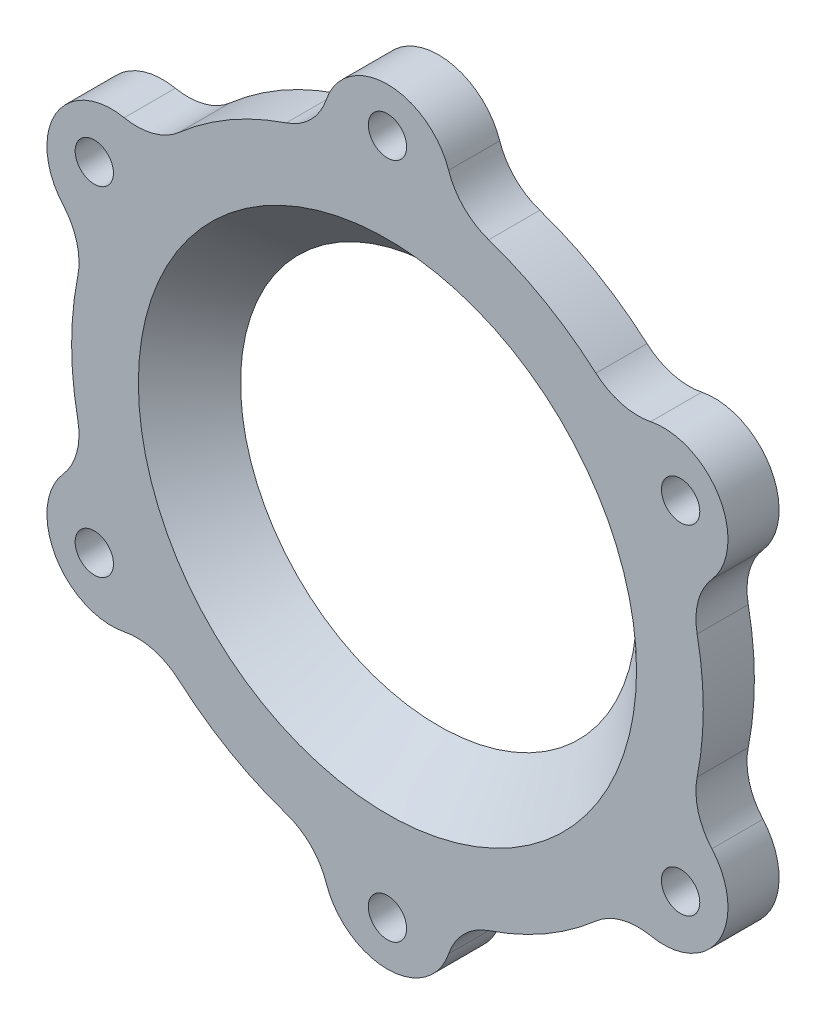
SolidWorks part; units mm, degrees
material "6063-T6"
ref_plane "Front Plane" through (0, 0, 0) normal (0, 0, 1) x (1, 0, 0)
ref_plane "Top Plane" through (0, 0, 0) normal (0, 1, 0) x (1, 0, 0)
ref_plane "Right Plane" through (0, 0, 0) normal (1, 0, 0) x (0, 0, -1)
sketch "Sketch5" plane through (0, 0, 0) normal (0, 1, 0) x (1, 0, 0)
  line L0 (0, -16.5008) -> (0, 15.0181) construction
ref_plane "Plane1" through (0, 0, 0) normal (-0.5, 0.866, 0) x (0, 0, -1)
sketch "Sketch2" plane through (0, 0, 0) normal (0, 0, 1) x (1, 0, 0)
  line L0 (0, 0) -> (0, 53) construction
  line L1 (0, 0) -> (0, 40) construction
  line L2 (0, 0) -> (0, 53) construction
  circle A0 centre (0, 0) radius 31
  circle A1 centre (0, 0) radius 60
  circle A2 centre (0, 53) radius 3
  circle A3 centre (45.8993, 26.5) radius 3
  circle A4 centre (45.8993, -26.5) radius 3
  circle A5 centre (0, -53) radius 3
  circle A6 centre (-45.8993, -26.5) radius 3
  circle A7 centre (-45.8993, 26.5) radius 3
  circle A11 centre (0, 0) radius 53 construction
  circle A18 centre (0, 0) radius 46.95 construction
  arc A19 (-15.849, 46.8413) -> (15.849, 46.8413) centre (0, 0) ccw
  arc A21 (-9.5776, 53.1206) -> (9.5776, 53.1206) centre (0, 49.8933) cw
  arc A22 (9.5776, 53.1206) -> (15.849, 46.8413) centre (19.0541, 56.3138) ccw
  circle A23 centre (0, 0) radius 49.45 construction
  arc A24 (-9.5776, 53.1206) -> (-15.849, 46.8413) centre (-19.0541, 56.3138) cw
  arc A25 (41.215, 34.8547) -> (50.7926, 18.2658) centre (43.2088, 24.9466) cw
  arc A26 (41.215, 34.8547) -> (32.6413, 37.1463) centre (39.2422, 44.6582) cw
  arc A27 (50.7926, 18.2658) -> (48.4903, 9.695) centre (58.2962, 11.6556) ccw
  arc A28 (50.7926, -18.2658) -> (41.215, -34.8547) centre (43.2088, -24.9466) cw
  arc A29 (50.7926, -18.2658) -> (48.4903, -9.695) centre (58.2962, -11.6556) cw
  arc A30 (41.215, -34.8547) -> (32.6413, -37.1463) centre (39.2422, -44.6582) ccw
  arc A31 (9.5776, -53.1206) -> (-9.5776, -53.1206) centre (0, -49.8933) cw
  arc A32 (9.5776, -53.1206) -> (15.849, -46.8413) centre (19.0541, -56.3138) cw
  arc A33 (-9.5776, -53.1206) -> (-15.849, -46.8413) centre (-19.0541, -56.3138) ccw
  arc A34 (-41.215, -34.8547) -> (-50.7926, -18.2658) centre (-43.2088, -24.9466) cw
  arc A35 (-41.215, -34.8547) -> (-32.6413, -37.1463) centre (-39.2422, -44.6582) cw
  arc A36 (-50.7926, -18.2658) -> (-48.4903, -9.695) centre (-58.2962, -11.6556) ccw
  arc A37 (-50.7926, 18.2658) -> (-41.215, 34.8547) centre (-43.2088, 24.9466) cw
  arc A38 (-50.7926, 18.2658) -> (-48.4903, 9.695) centre (-58.2962, 11.6556) cw
  arc A39 (-41.215, 34.8547) -> (-32.6413, 37.1463) centre (-39.2422, 44.6582) ccw
  point P24 (0, 0)
  point P42 (46.95, 0)
  point P43 (0, 0)
  point P46 (10, 48.4283)
  point P49 (-10, 48.4283)
  point P84 (0, 0)
  dimension "D1" = 6
  dimension "D2" = 62
  dimension "D3" = 120
  dimension "D7" = 93.9
  dimension "D12" = 10
  dimension "D10" = 40
  dimension "D4" = 0
  dimension "D11" = 20
  dimension "D8" = 2.5
  dimension "D5" = 6
  dimension "D13" = 6
extrude "Boss-Extrude1" add sketch "Sketch2" along normal blind 8 contours A21 A24 A19 A22 A0 A2 | A39 A37 A38 A19 A7 | A27 A25 A26 A19 A3 | A33 A31 A32 A19 A5 | A36 A34 A35 A19 A6 | A30 A28 A29 A19 A4 region at (52.9238, 23.9788, 0) region at (47.2282, -33.844, 0) region at (5.0355, 56.9038, 0) region at (-5.6959, -57.8232, 0) region at (-47.2282, 33.844, 0) region at (-52.9238, -23.9788, 0)
sketch "Sketch4" plane through (0, 0, 0) normal (-0.5, 0.866, 0) x (0, 0, -1)
  line L0 (0, 0) -> (-8, 0) construction
  line L3 (-16.5008, 0) -> (15.0181, 0) construction
  line L7 (0, -9.695) -> (0, 9.695)
  line L8 (0, 9.695) -> (-8, 9.695)
  line L9 (-8, 9.695) -> (-8, -9.695)
  line L10 (-8, -9.695) -> (0, -9.695)
  line L11 (0, -9.695) -> (0, 9.695)
  line L12 (0, 9.695) -> (-8, 9.695)
  line L13 (-8, 9.695) -> (-8, -9.695)
  line L14 (-8, -9.695) -> (0, -9.695)
  circle A4 centre (-4, 0) radius 2.1
  dimension "D1" = 0
  dimension "D2" = 4.2
chamfer "Chamfer1" distance 8 angle 45 1 edges at (31, 0, 8)
equation "\"D7@Sketch2\"=88.900000+5mm"
